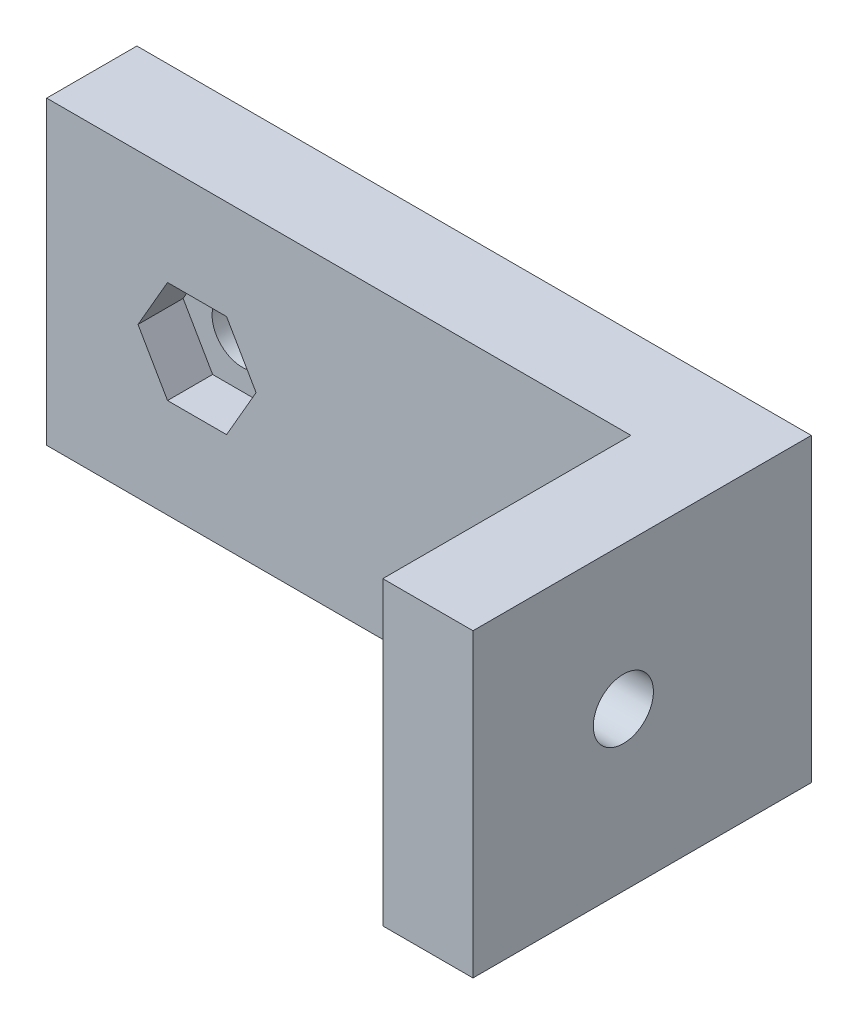
SolidWorks part; units mm, degrees
material "ABS"
ref_plane "Front Plane" through (0, 0, 0) normal (0, 0, 1) x (1, 0, 0)
ref_plane "Top Plane" through (0, 0, 0) normal (0, 1, 0) x (1, 0, 0)
ref_plane "Right Plane" through (0, 0, 0) normal (1, 0, 0) x (0, 0, -1)
sketch "Sketch1" plane through (0, 0, 0) normal (0, 0, 1) x (1, 0, 0)
  line L0 (169.7, 145.6824) -> (169.7, 86.2) construction
  line L1 (169.7, -7.5) -> (124.85, -7.5)
  line L2 (169.7, -7.5) -> (169.7, 12.5)
  line L3 (169.7, 12.5) -> (124.85, 12.5)
  line L4 (124.85, -7.5) -> (124.85, 12.5)
  line L5 (169.7, -7.5) -> (124.85, 12.5) construction
  line L6 (169.7, 12.5) -> (124.85, -7.5) construction
  line L8 (130.924, 2.5) -> (132.887, -0.9)
  line L9 (132.887, -0.9) -> (136.813, -0.9)
  line L10 (136.813, -0.9) -> (138.776, 2.5)
  line L11 (138.776, 2.5) -> (136.813, 5.9)
  line L12 (136.813, 5.9) -> (132.887, 5.9)
  line L13 (132.887, 5.9) -> (130.924, 2.5)
  circle A0 centre (134.85, 2.5) radius 2
  circle A1 centre (134.85, 2.5) radius 3.4 construction
  point P4 (147.275, 2.5)
  point P10 (134.85, 5.9)
  dimension "D2" = 10
  dimension "D3" = 10
  dimension "D4" = 10
  dimension "D1" = 6.8
extrude "Boss-Extrude1" add sketch "Sketch1" along normal blind 3 contours L4 L1 L2 L3 L13 L12 L11 L10 L9 L8 | L12 L13 L8 L9 L10 L11 A0 region at (147.8556, 2.5, 0) region at (131.9955, 4.1481, 0)
extrude "Boss-Extrude2" add sketch "Sketch1<4>" along normal blind 3 from surface contours L4 L1 L2 L3 L13 L12 L11 L10 L9 L8 region at (147.8556, 2.5, 0) starting at face at (147.275, 2.5, 3)
sketch "Sketch1<4>" plane through (0, 0, 0) normal (0, 0, 1) x (1, 0, 0) same geometry as "Sketch1"
sketch "Sketch5" plane through (169.7, 0, 0) normal (-1, 0, 0) x (0, 0, 1)
  line L0 (6, 12.5) -> (0, 12.5) construction
  line L1 (6, -7.5) -> (22.5, -7.5)
  line L2 (6, -7.5) -> (6, 12.5)
  line L3 (6, 12.5) -> (22.5, 12.5)
  line L4 (22.5, -7.5) -> (22.5, 12.5)
  line L5 (6, -7.5) -> (22.5, 12.5) construction
  line L6 (6, 12.5) -> (22.5, -7.5) construction
  line L8 (12.5, -0.926) -> (15.9, 1.037)
  line L9 (15.9, 1.037) -> (15.9, 4.963)
  line L10 (15.9, 4.963) -> (12.5, 6.926)
  line L11 (12.5, 6.926) -> (9.1, 4.963)
  line L12 (9.1, 4.963) -> (9.1, 1.037)
  line L13 (9.1, 1.037) -> (12.5, -0.926)
  circle A0 centre (12.5, 3) radius 2
  circle A1 centre (12.5, 3) radius 3.4 construction
  point P7 (14.25, 2.5)
  circle M18 centre (12.5, 3) radius 2
  dimension "D1" = 10
  dimension "D2" = 6.8
extrude "Boss-Extrude3" add sketch "Sketch5" along normal blind 3 contours L1 L4 L3 L2 L13 L12 L11 L10 L9 L8 | L12 L13 L8 L9 L10 L11 M18 region at (169.7, 2.5, 6.2593) region at (169.7, 0.1455, 10.8519)
extrude "Boss-Extrude4" add sketch "Sketch5<3>" along normal blind 3 from surface contours L1 L4 L3 L2 L13 L12 L11 L10 L9 L8 region at (169.7, 2.5, 6.2593) starting at face at (166.7, 2.5, 14.25)
sketch "Sketch5<3>" plane through (169.7, 0, 0) normal (-1, 0, 0) x (0, 0, 1) same geometry as "Sketch5"
